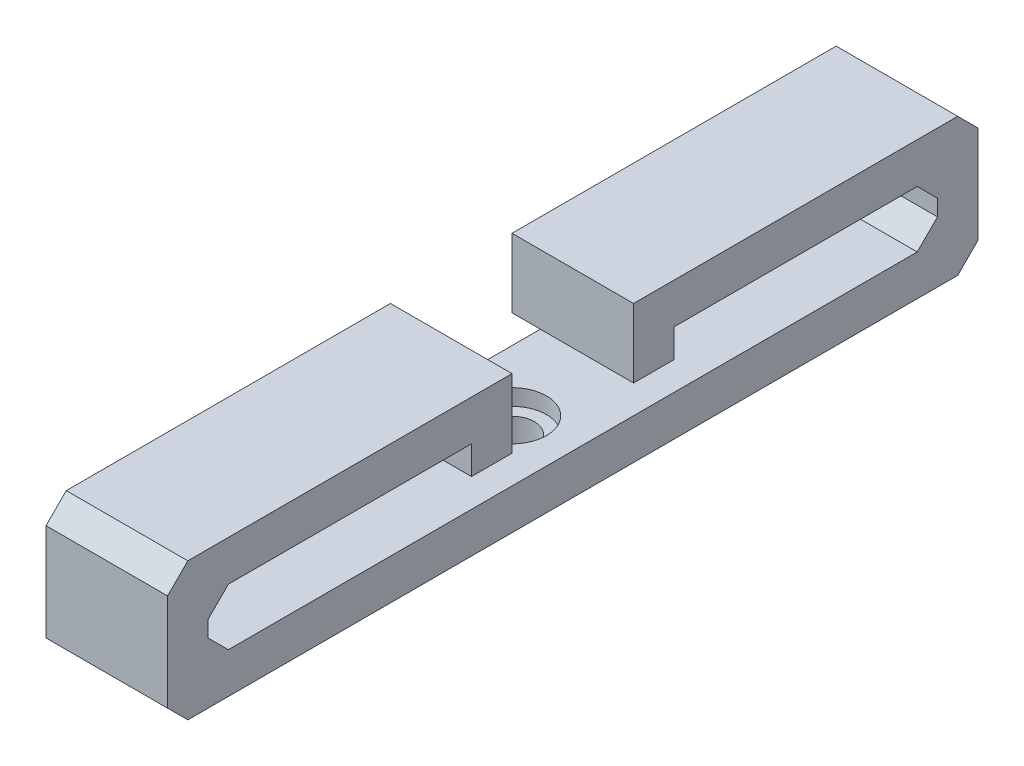
SolidWorks part; units mm, degrees
ref_plane "Front Plane" through (0, 0, 0) normal (0, 0, 1) x (1, 0, 0)
ref_plane "Top Plane" through (0, 0, 0) normal (0, 1, 0) x (1, 0, 0)
ref_plane "Right Plane" through (0, 0, 0) normal (1, 0, 0) x (0, 0, -1)
sketch "Sketch1" plane through (0, 0, 0) normal (1, 0, 0) x (0, 0, -1)
  line L0 (7.5, 17) -> (7.5, 12)
  line L1 (7.5, 12) -> (45, 12)
  line L2 (45, 12) -> (45, 5)
  line L3 (45, 5) -> (-45, 5)
  line L5 (-50, 0) -> (50, 0)
  line L6 (50, 0) -> (50, 17)
  line L7 (50, 17) -> (7.5, 17)
  line L8 (0, 5) -> (0, 0) construction
  line L9 (-45, 12) -> (-45, 5)
  line L10 (-7.5, 17) -> (-7.5, 12)
  line L11 (-50, 17) -> (-7.5, 17)
  line L12 (-7.5, 12) -> (-45, 12)
  line L13 (-50, 0) -> (-50, 17)
  dimension "D1" = 7
  dimension "D2" = 50
  dimension "D3" = 5
  dimension "D4" = 5
  dimension "D5" = 7.5
  dimension "D6" = 5
extrude "Boss-Extrude1" add sketch "Sketch1" along normal mid plane 15
chamfer "Chamfer1" distance 2.5 angle 45 8 edges at (0, 12, -45) (0, 17, -50) (0, 12, 45) (0, 17, 50) (0, 0, -50) (0, 5, -45) (0, 0, 50) (0, 5, 45)
sketch "Sketch2" plane through (0, 5, 0) normal (0, 1, 0) x (1, 0, 0)
  circle A0 centre (0, 0) radius 2.75
  dimension "D1" = 5.5
extrude "Cut-Extrude1" cut sketch "Sketch2" against normal through all
sketch "Sketch3" plane through (0, 5, 0) normal (0, 1, 0) x (1, 0, 0)
  circle A0 centre (0, 0) radius 4.25
  dimension "D1" = 8.5
extrude "Cut-Extrude2" cut sketch "Sketch3" against normal blind 2
sketch "Sketch4" plane through (-7.5, 0, 0) normal (-1, 0, 0) x (0, 0, 1)
  line L0 (-42.5, 5) -> (42.5, 5) construction
  line L1 (-7.5, 17) -> (-12.5, 17)
  line L2 (-7.5, 17) -> (-7.5, 8.5)
  line L3 (-7.5, 8.5) -> (-12.5, 8.5)
  line L4 (-12.5, 17) -> (-12.5, 8.5)
  dimension "D1" = 5
  dimension "D2" = 3.5
extrude "Boss-Extrude2" add sketch "Sketch4" against normal up to surface (15 mm away) up to face at (7.5, 9.7, 0)
mirror "Mirror1" about plane through (0, 0, 0) normal (0, 0, 1) of "Boss-Extrude2"
